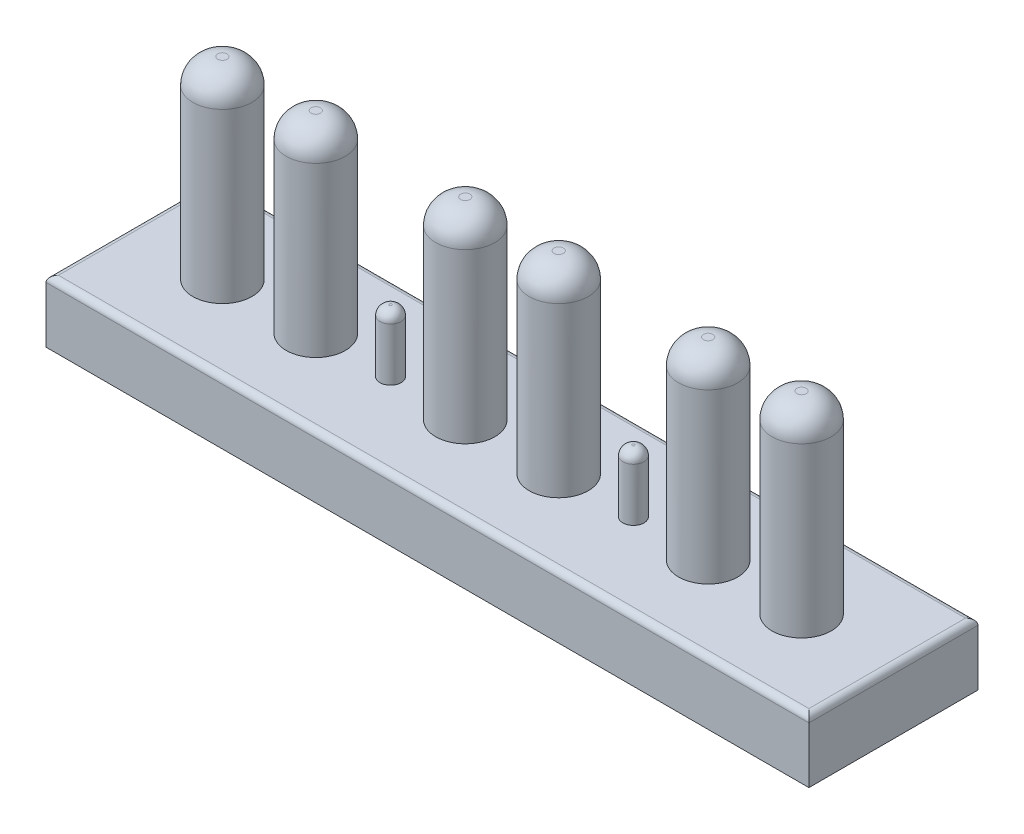
SolidWorks part; units mm, degrees
other "Marquage1"
sketch "Esquisse3"
ref_plane "Front Plane" through (0, 0, 0) normal (0, 0, 1) x (1, 0, 0)
ref_plane "Top Plane" through (0, 0, 0) normal (0, 1, 0) x (1, 0, 0)
ref_plane "Right Plane" through (0, 0, 0) normal (1, 0, 0) x (0, 0, -1)
sketch "Esquisse2" plane through (0, 0, 0) normal (0, 1, 0) x (1, 0, 0)
  line L0 (164.7492, 0) -> (-148.4452, 0) construction
  circle A0 centre (32.4575, 0) radius 9.5
  circle A1 centre (62.4575, 0) radius 9.5
  circle A2 centre (-123.5425, 0) radius 9.5
  circle A3 centre (-93.5425, 0) radius 9.5
  circle A4 centre (-45.5425, 0) radius 9.5
  circle A5 centre (-15.5425, 0) radius 9.5
  circle A6 centre (-69.5425, 0) radius 3.4
  circle A7 centre (8.4575, 0) radius 3.4
  point P8 (0, 0)
  point P11 (0, 0)
  point P12 (0, 0)
  point P15 (0, 0)
  point P16 (0, 0)
  dimension "D1" = 30
  dimension "D2" = 30
  dimension "D3" = 24
  dimension "D4" = 24
  dimension "D5" = 30
  dimension "D6" = 24
  dimension "D7" = 24
extrude "Boss.-Extru.1" add sketch "Esquisse2" along normal blind 62 contours A1 | A0 | A2 | A5 | A4 | A3
extrude "Boss.-Extru.2" add sketch "Esquisse2<4>" along normal blind 20
sketch "Esquisse2<4>" plane through (0, 0, 0) normal (0, 1, 0) x (1, 0, 0) same geometry as "Esquisse2"
fillet "Congé3" radius 8 1 edges at (-123.5425, 62, 9.5)
fillet "Congé4" radius 8 1 edges at (-93.5425, 62, 9.5)
fillet "Congé5" radius 8 1 edges at (-45.5425, 62, 9.5)
fillet "Congé6" radius 8 1 edges at (-15.5425, 62, 9.5)
fillet "Congé7" radius 8 1 edges at (32.4575, 62, 9.5)
fillet "Congé8" radius 8 1 edges at (62.4575, 62, 9.5)
fillet "Congé10" radius 3 1 edges at (-69.5425, 20, 3.4)
sketch "Esquisse4" plane through (0, 0, 0) normal (0, -1, 0) x (-1, 0, 0)
  line L1 (-91.9575, 27.1466) -> (153.0425, 27.1466)
  line L2 (-91.9575, 27.1466) -> (-91.9575, -27.1466)
  line L3 (-91.9575, -27.1466) -> (153.0425, -27.1466)
  line L4 (153.0425, 27.1466) -> (153.0425, -27.1466)
  line L5 (-91.9575, 27.1466) -> (153.0425, -27.1466) construction
  line L6 (-91.9575, -27.1466) -> (153.0425, 27.1466) construction
  circle A3 centre (-62.4575, 0) radius 9.5 construction
  circle A4 centre (123.5425, 0) radius 9.5 construction
  point P0 (0, 0)
  point P8 (0, 0)
  dimension "D1" = 29.5
  dimension "D2" = 29.5
fillet "Congé11" radius 3 1 edges at (8.4575, 20, 3.4)
extrude "Boss.-Extru.3" add sketch "Esquisse4" along normal blind 20
fillet "Congé12" radius 2 4 edges at (-153.0425, 0, 0) (-30.5425, 0, 27.1466) (91.9575, 0, 0) (-30.5425, 0, -27.1466)
